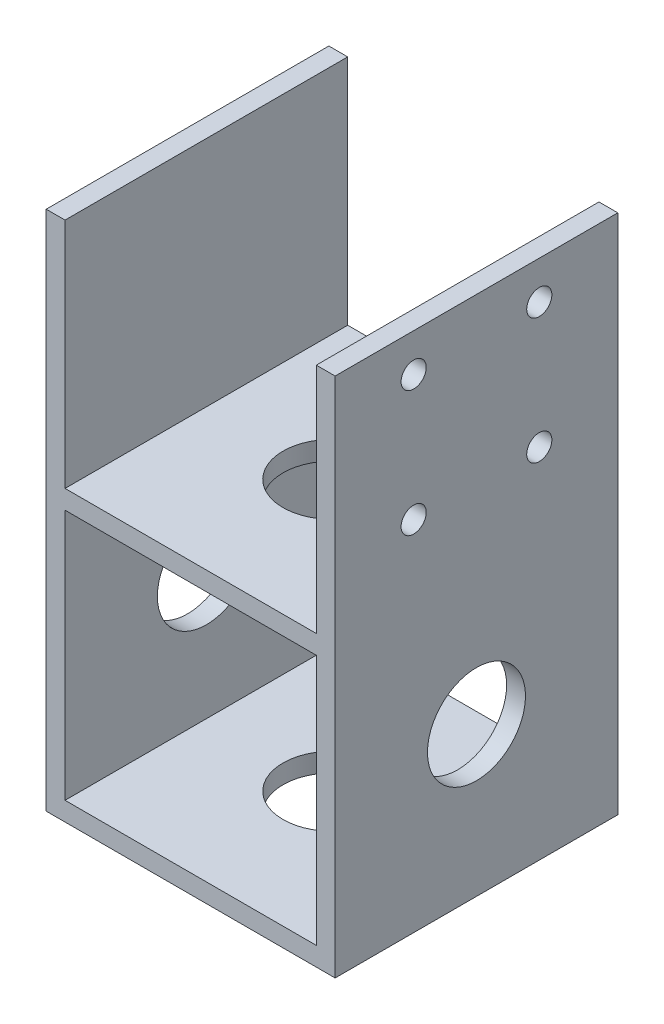
SolidWorks part; units mm, degrees
material "6061 Alloy"
ref_plane "Front Plane" through (0, 0, 0) normal (0, 0, 1) x (1, 0, 0)
ref_plane "Top Plane" through (0, 0, 0) normal (0, 1, 0) x (1, 0, 0)
ref_plane "Right Plane" through (0, 0, 0) normal (1, 0, 0) x (0, 0, -1)
sketch "Sketch1" plane through (0, 0, 0) normal (0, 1, 0) x (1, 0, 0)
  line L1 (23, -22.5) -> (-23, -22.5)
  line L2 (23, -22.5) -> (23, 22.5)
  line L3 (23, 22.5) -> (-23, 22.5)
  line L4 (-23, -22.5) -> (-23, 22.5)
  line L5 (23, -22.5) -> (-23, 22.5) construction
  line L6 (23, 22.5) -> (-23, -22.5) construction
  point P1 (0, 0)
  dimension "50" = 46
  dimension "D2" = 45
extrude "Boss-Extrude1" add sketch "Sketch1" along normal blind 3
sketch "Sketch5" plane through (0, 3, 0) normal (0, 1, 0) x (1, 0, 0)
  line L0 (-23, -22.5) -> (23, -22.5) construction
  line L1 (23, 22.5) -> (20, 22.5)
  line L2 (23, 22.5) -> (23, -22.5)
  line L3 (23, -22.5) -> (20, -22.5)
  line L4 (20, 22.5) -> (20, -22.5)
  line L7 (-23, 22.5) -> (-20, 22.5)
  line L8 (-23, 22.5) -> (-23, -22.5)
  line L9 (-23, -22.5) -> (-20, -22.5)
  line L10 (-20, 22.5) -> (-20, -22.5)
  dimension "D1" = 3
  dimension "D2" = 3
extrude "Boss-Extrude3" add sketch "Sketch5" along normal blind 35
sketch "Sketch9" plane through (0, 3, 0) normal (0, 1, 0) x (1, 0, 0)
  circle A0 centre (0, 0) radius 7.8
extrude "Cut-Extrude5" cut sketch "Sketch9" against normal blind 10
sketch "Sketch11" plane through (-23, 0, 0) normal (-1, 0, 0) x (0, 0, 1)
  line L0 (0, 0) -> (0, 38) construction
  line L5 (-22.5, 0) -> (22.5, 0) construction
  line L6 (-22.5, 38) -> (22.5, 38) construction
  line L7 (0, 38) -> (0, 19) construction
  line L8 (0, 19) -> (0, 28.5) construction
  line L9 (0, 28.5) -> (0, 19)
  circle A1 centre (0, 23.75) radius 7.8
extrude "Cut-Extrude8" cut sketch "Sketch11" against normal through all contours A1 region at (-23, 23.75, -7.5794)
sketch "Sketch12" plane through (0, 38, 0) normal (0, 1, 0) x (1, 0, 0)
  line L0 (-23, 22.5) -> (-20, 22.5)
  line L1 (-23, 22.5) -> (-23, -22.5)
  line L2 (-20, 22.5) -> (-20, -22.5)
  line L3 (-23, -22.5) -> (-20, -22.5)
  line L4 (20, 22.5) -> (23, 22.5)
  line L5 (20, 22.5) -> (20, -22.5)
  line L6 (23, 22.5) -> (23, -22.5)
  line L7 (20, -22.5) -> (23, -22.5)
  line L8 (20, -22.5) -> (23, -22.5) construction
  line L9 (-23, -22.5) -> (-20, -22.5) construction
extrude "Boss-Extrude4" add sketch "Sketch12" along normal blind 45
sketch "Sketch13" plane through (23, 0, 0) normal (1, 0, 0) x (0, 0, -1)
  line L0 (0, 83) -> (0, 31.55) construction
  line L1 (-22.5, 83) -> (22.5, 83) construction
  line L2 (0, 66.9557) -> (22.5, 66.9557) construction
  line L3 (22.5, 83) -> (22.5, 0) construction
  circle A0 centre (-10, 76.9557) radius 2
  circle A2 centre (0, 23.75) radius 7.8 construction
  circle A3 centre (10, 76.9557) radius 2
  circle A4 centre (10, 56.9557) radius 2
  circle A5 centre (-10, 56.9557) radius 2
  dimension "D3" = 4
  dimension "D1" = 10
  dimension "D2" = 10
extrude "Cut-Extrude9" cut sketch "Sketch13" against normal blind 10
ref_plane "Plane1" through (0, 23, 0) normal (0, 1, 0) x (1, 0, 0)
mirror "Mirror1" about plane through (0, 23, 0) normal (0, 1, 0) of "Cut-Extrude5", "Boss-Extrude1"
sketch "Sketch15" plane through (0, 83, 0) normal (0, 1, 0) x (1, 0, 0)
  line L0 (-23, 22.5) -> (23, 22.5)
  line L1 (-23, 22.5) -> (-23, -22.526)
  line L2 (23, 22.5) -> (23, -22.526)
  line L3 (-23, -22.526) -> (23, -22.526)
extrude "Boss-Extrude5" [suppressed] add sketch "Sketch15" along normal blind 3
sketch "Sketch16" [suppressed] plane through (0, 86, 0) normal (0, 1, 0) x (1, 0, 0)
  circle A0 centre (0, 0) radius 10.5
  circle A1 centre (0, 0) radius 13 construction
  circle A2 centre (0, 13) radius 1.5
  circle A3 centre (13, 0) radius 1.5
  circle A4 centre (0, -13) radius 1.5
  circle A5 centre (-13, 0) radius 1.5
  point P15 (0, 0)
  dimension "D1" = 21
  dimension "D2" = 3
  dimension "D4" = 26
  dimension "D3" = 4
extrude "Cut-Extrude10" [suppressed] cut sketch "Sketch16" against normal blind 3
